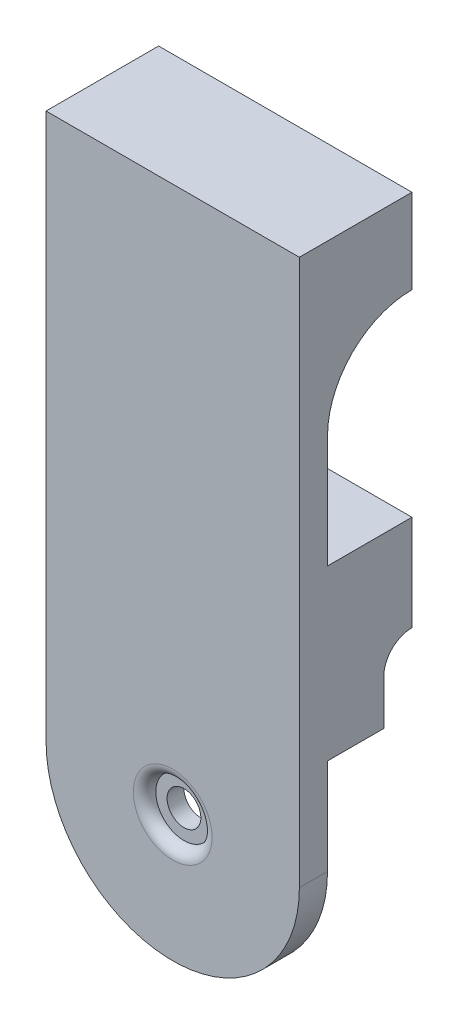
SolidWorks part; units mm, degrees
ref_plane "Front Plane" through (0, 0, 0) normal (0, 0, 1) x (1, 0, 0)
ref_plane "Top Plane" through (0, 0, 0) normal (0, 1, 0) x (1, 0, 0)
ref_plane "Right Plane" through (0, 0, 0) normal (1, 0, 0) x (0, 0, -1)
sketch "Esboço2" plane through (0, 0, 0) normal (0, 0, 1) x (1, 0, 0)
  line L0 (-22.5, 0) -> (-22.5, 30)
  line L1 (-22.5, 30) -> (22.5, 30)
  line L2 (22.5, 30) -> (22.5, 0)
  circle A0 centre (0, 0) radius 3
  arc A1 (-22.5, 0) -> (22.5, 0) centre (0, 0) ccw
  dimension "D1" = 6
  dimension "D2" = 22.5
  dimension "D3" = 30
  dimension "D4" = 45
extrude "Ressalto-extrusão1" add sketch "Esboço2" along normal blind 5
sketch "Esboço11" plane through (0, 0, 5) normal (0, 0, 1) x (1, 0, 0)
  circle A0 centre (0, 0) radius 5
  dimension "D1" = 10
extrude "Corte-extrusão3" cut sketch "Esboço11" against normal blind 2
sketch "Esboço3" plane through (0, 0, 0) normal (0, 0, -1) x (-1, 0, 0)
  line L0 (-22.5, 17) -> (22.5, 17)
  line L1 (-22.5, 0) -> (-22.5, 30) construction
  line L2 (22.5, 30) -> (22.5, 0) construction
  line L3 (22.5, 17) -> (22.5, 30)
  line L4 (22.5, 30) -> (-22.5, 30)
  line L5 (-22.5, 30) -> (-22.5, 17)
  line L6 (-22.5, 30) -> (22.5, 30) construction
  dimension "D1" = 17
extrude "Ressalto-extrusão2" add sketch "Esboço3" along normal blind 10
sketch "Esboço4" plane through (0, 30, 0) normal (0, 1, 0) x (1, 0, 0)
  line L14 (-22.5, -5) -> (-22.5, 15)
  line L15 (-22.5, 15) -> (22.5, 15)
  line L16 (22.5, 15) -> (22.5, -5)
  line L17 (22.5, -5) -> (-22.5, -5)
  dimension "D1" = 20
extrude "Ressalto-extrusão3" add sketch "Esboço4" along normal blind 17
sketch "Esboço6" plane through (0, 0, -15) normal (0, 0, -1) x (-1, 0, 0)
  line L0 (22.5, 47) -> (22.5, 30) construction
  line L1 (-22.5, 30) -> (22.5, 30) construction
  line L2 (-22.5, 47) -> (-22.5, 30) construction
  line L3 (-22.5, 47) -> (22.5, 47) construction
  line L4 (22.5, 47) -> (22.5, 30)
  line L5 (-22.5, 30) -> (22.5, 30)
  line L6 (-22.5, 47) -> (-22.5, 30)
  line L7 (-22.5, 47) -> (22.5, 47)
  line L8 (15.25, 41.75) -> (15.25, 35.25)
  line L9 (-15.25, 35.25) -> (15.25, 35.25)
  line L10 (-15.25, 41.75) -> (-15.25, 35.25)
  line L11 (-15.25, 41.75) -> (15.25, 41.75)
  point P8 (15.25, 38.5)
  point P9 (22.5, 38.5)
  point P10 (0, 41.75)
  point P11 (0, 47)
  dimension "D1" = 6.5
  dimension "D2" = 30.5
extrude "Corte-extrusão1" cut sketch "Esboço6" against normal blind 15 contours L8 L9 L10 L11
sketch "Esboço7" plane through (0, 47, 0) normal (0, 1, 0) x (1, 0, 0)
  line L0 (22.5, -5) -> (22.5, 15) construction
  line L1 (-22.5, -5) -> (22.5, -5)
  line L2 (-22.5, -5) -> (-22.5, 0)
  line L3 (-22.5, 0) -> (22.5, 0)
  line L4 (22.5, -5) -> (22.5, 0)
  point P9 (0, 0)
extrude "Ressalto-extrusão4" add sketch "Esboço7" along normal blind 50
sketch "Esboço8" plane through (0, 0, 0) normal (0, 0, -1) x (-1, 0, 0)
  line L0 (22.5, 97) -> (22.5, 47) construction
  line L1 (-22.5, 97) -> (22.5, 97)
  line L2 (-22.5, 97) -> (-22.5, 82)
  line L3 (-22.5, 82) -> (22.5, 82)
  line L4 (22.5, 97) -> (22.5, 82)
  dimension "D1" = 15
extrude "Ressalto-extrusão5" add sketch "Esboço8" along normal blind 15
sketch "Esboço9" plane through (0, 0, -15) normal (0, 0, -1) x (-1, 0, 0)
  line L0 (22.5, 82) -> (22.5, 97) construction
  line L1 (-17.75, 86.75) -> (17.75, 86.75)
  line L2 (-17.75, 86.75) -> (-17.75, 92.25)
  line L3 (-17.75, 92.25) -> (17.75, 92.25)
  line L4 (17.75, 86.75) -> (17.75, 92.25)
  line L10 (22.5, 97) -> (-22.5, 97) construction
  dimension "D1" = 5.5
  dimension "D2" = 35.5
  dimension "D3" = 4.75
  dimension "D4" = 4.75
extrude "Corte-extrusão2" cut sketch "Esboço9" against normal blind 15
fillet "Filete4" radius 5 1 edges at (0, 30, -10)
fillet "Filete6" radius 15 1 edges at (0, 82, 0)
fillet "Filete7" radius 2 1 edges at (5, 0, 5)
